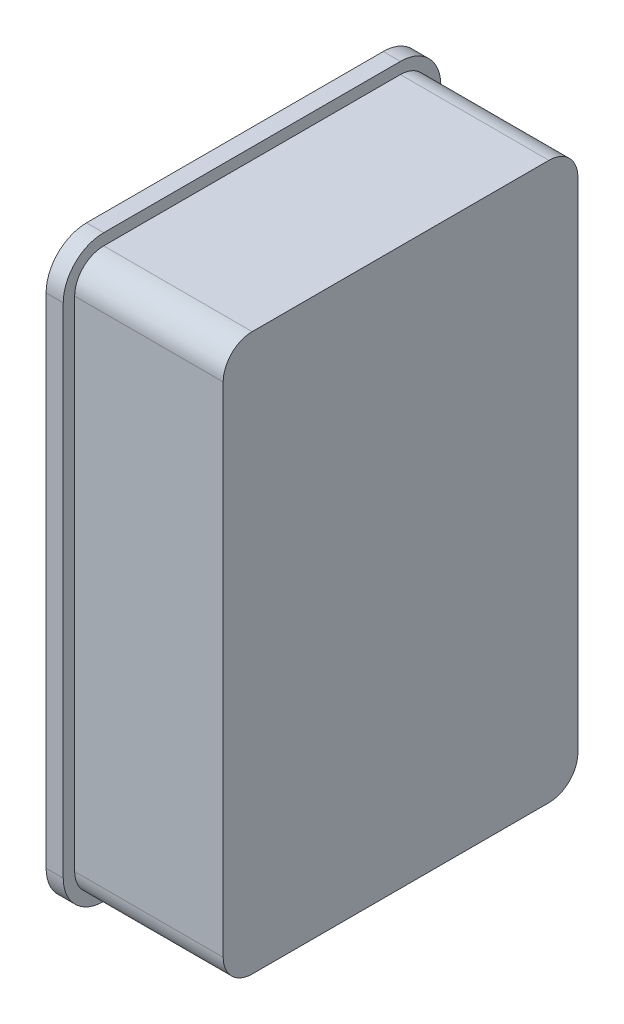
SolidWorks part; units mm, degrees
ref_plane "Top Plane" through (0, 0, 0) normal (0, 0, 1) x (1, 0, 0)
ref_plane "Right Plane" through (0, 0, 0) normal (0, 1, 0) x (1, 0, 0)
ref_plane "Front Plane" through (0, 0, 0) normal (1, 0, 0) x (0, 0, -1)
ref_axis "x-axis" through (-88.99, 0, 0) along (1, 0, 0)
ref_axis "y-axis" through (0, -55, 0) along (0, 1, 0)
ref_axis "z-axis" through (0, 0, 55) along (0, 0, -1)
sketch "Sketch2" plane through (0, 0, 0) normal (1, 0, 0) x (0, -1, 0)
  line L8 (6.35, 2.54) -> (6.35, 28.51)
  line L9 (3.81, 31.05) -> (-39.81, 31.05)
  line L10 (-42.35, 28.51) -> (-42.35, 2.54)
  line L11 (-39.81, 0) -> (3.81, 0)
  line L12 (0, 21.525) -> (0, 9.525)
  line L13 (0, 9.525) -> (-36, 9.525)
  line L14 (-36, 9.525) -> (-36, 21.525)
  line L15 (-36, 21.525) -> (0, 21.525)
  arc A8 (3.81, 0) -> (6.35, 2.54) centre (3.81, 2.54) ccw
  arc A9 (6.35, 28.51) -> (3.81, 31.05) centre (3.81, 28.51) ccw
  arc A10 (-39.81, 31.05) -> (-42.35, 28.51) centre (-39.81, 28.51) ccw
  arc A11 (-42.35, 2.54) -> (-39.81, 0) centre (-39.81, 2.54) ccw
  point P13 (0, 0)
  point P18 (-35.9164, 9.525)
extrude "Boss-Extrude2" add sketch "Sketch2" along normal blind 12
sketch "Sketch3" plane through (12, 0, 0) normal (1, 0, 0) x (0, 1, 0)
  line L4 (-6.35, -2.54) -> (-6.35, -28.51)
  line L5 (-3.81, -31.05) -> (39.81, -31.05)
  line L6 (42.35, -28.51) -> (42.35, -2.54)
  line L7 (39.81, 0) -> (-3.81, 0)
  line L8 (-6.35, -2.54) -> (-6.35, -28.51)
  line L9 (-3.81, -31.05) -> (39.81, -31.05)
  line L10 (42.35, -28.51) -> (42.35, -2.54)
  line L11 (39.81, 0) -> (-3.81, 0)
  arc A4 (-3.81, 0) -> (-6.35, -2.54) centre (-3.81, -2.54) ccw
  arc A5 (-6.35, -28.51) -> (-3.81, -31.05) centre (-3.81, -28.51) ccw
  arc A6 (39.81, -31.05) -> (42.35, -28.51) centre (39.81, -28.51) ccw
  arc A7 (42.35, -2.54) -> (39.81, 0) centre (39.81, -2.54) ccw
  arc A8 (-3.81, 0) -> (-6.35, -2.54) centre (-3.81, -2.54) ccw
  arc A9 (-6.35, -28.51) -> (-3.81, -31.05) centre (-3.81, -28.51) ccw
  arc A10 (39.81, -31.05) -> (42.35, -28.51) centre (39.81, -28.51) ccw
  arc A11 (42.35, -2.54) -> (39.81, 0) centre (39.81, -2.54) ccw
  dimension "D1" = 0
extrude "Boss-Extrude3" add sketch "Sketch3" along normal blind 1
sketch "Sketch6" plane through (0, 0, 0) normal (-1, 0, 0) x (0, -1, 0)
  line L0 (6.35, -2.54) -> (6.35, -28.51) construction
  line L1 (3.81, -31.05) -> (-39.81, -31.05) construction
  line L2 (-42.35, -28.51) -> (-42.35, -2.54) construction
  line L3 (-39.81, 0) -> (3.81, 0) construction
  line L4 (6.35, -2.54) -> (6.35, -28.51)
  line L5 (3.81, -31.05) -> (-39.81, -31.05)
  line L6 (-42.35, -28.51) -> (-42.35, -2.54)
  line L7 (-39.81, 0) -> (3.81, 0)
  line L8 (7.35, -2.54) -> (7.35, -28.51)
  line L9 (3.81, -32.05) -> (-39.81, -32.05)
  line L10 (-43.35, -28.51) -> (-43.35, -2.54)
  line L11 (-39.81, 1) -> (3.81, 1)
  arc A0 (6.35, -2.54) -> (3.81, 0) centre (3.81, -2.54) ccw construction
  arc A1 (3.81, -31.05) -> (6.35, -28.51) centre (3.81, -28.51) ccw construction
  arc A2 (-42.35, -28.51) -> (-39.81, -31.05) centre (-39.81, -28.51) ccw construction
  arc A3 (-39.81, 0) -> (-42.35, -2.54) centre (-39.81, -2.54) ccw construction
  arc A4 (6.35, -2.54) -> (3.81, 0) centre (3.81, -2.54) ccw
  arc A5 (3.81, -31.05) -> (6.35, -28.51) centre (3.81, -28.51) ccw
  arc A6 (-42.35, -28.51) -> (-39.81, -31.05) centre (-39.81, -28.51) ccw
  arc A7 (-39.81, 0) -> (-42.35, -2.54) centre (-39.81, -2.54) ccw
  arc A8 (3.81, -32.05) -> (7.35, -28.51) centre (3.81, -28.51) ccw
  arc A9 (-43.35, -28.51) -> (-39.81, -32.05) centre (-39.81, -28.51) ccw
  arc A10 (-39.81, 1) -> (-43.35, -2.54) centre (-39.81, -2.54) ccw
  arc A11 (7.35, -2.54) -> (3.81, 1) centre (3.81, -2.54) ccw
  dimension "D1" = 1
extrude "Boss-Extrude5" add sketch "Sketch6" along normal blind 1.5 separate body
ref_plane "Plane1" through (0, 18, 0) normal (0, 1, 0) x (1, 0, 0)
ref_plane "Plane2" through (0, 0, -15.525) normal (0, 0, -1) x (-1, 0, 0)
sketch "Sketch10" plane through (0, 18, 0) normal (0, 1, 0) x (1, 0, 0)
  line L0 (-1.1, 0) -> (-1.1, 2)
  line L1 (-1.1, 2) -> (-1.5, 1.6)
  line L2 (-1.5, 1.6) -> (-1.5, 0)
  line L3 (-1.5, 0) -> (-1.1, 0)
  line L4 (0, 0) -> (0, 2.54)
  line L5 (-1.5, 0) -> (0, 0)
  line L6 (-1.5, 2.54) -> (-1.5, 0)
  line L7 (0, 2.54) -> (-1.5, 2.54)
  line L8 (0, 0) -> (0, 2.54) construction
  line L9 (-1.5, 0) -> (0, 0) construction
  line L10 (-1.5, 2.54) -> (-1.5, 0) construction
  line L11 (0, 2.54) -> (-1.5, 2.54) construction
  line L12 (6.6, 15.525) -> (-6.6, 15.525) construction
  line L13 (0, 28.51) -> (-1.5, 28.51) construction
  line L14 (-1.5, 28.51) -> (-1.5, 31.05) construction
  line L15 (-1.5, 31.05) -> (0, 31.05) construction
  line L16 (0, 31.05) -> (0, 28.51) construction
  line L17 (-1.5, 31.05) -> (-1.1, 31.05)
  line L18 (-1.5, 30.45) -> (-1.5, 31.05)
  line L19 (-1.1, 30.05) -> (-1.5, 30.45)
  line L20 (-1.1, 31.05) -> (-1.1, 30.05)
  point P6 (0, 0)
  point P8 (0, 0)
  point P9 (-1.1, 1.9969)
  point P10 (0, 0)
  point P11 (-2, 0.5851)
  point P21 (0, 0)
  point P22 (0, 0)
  point P23 (0, 0)
  point P24 (-1.5, 29.95)
  point P25 (-1.5, 29.95)
  point P26 (-1.5, 31.05)
  point P27 (-1.5, 31.05)
  point P28 (-1.5, 29.55)
  point P29 (-1.5, 29.55)
  point P30 (-1.1, 29.95)
  point P31 (0, 0)
  point P32 (-1.048, 29.95)
  point P33 (-1.1125, 29.95)
  point P34 (-1.131, 29.2746)
  point P35 (-1.1, 29.2755)
  point P36 (0, 0)
  dimension "D2" = 1.1
  dimension "D3" = 2
  dimension "D4" = 45
  dimension "D5" = 45
  dimension "D6" = 1.1
  dimension "D7" = 1
  dimension "D1" = 0
extrude "Boss-Extrude10" add sketch "Sketch10" along normal up to surface and the other way up to surface up to face at (-0.75, 42.35, -15.525) other way up to face at (-0.75, -6.35, -15.525)
sketch "Sketch15" plane through (-1.5, 0, 0) normal (-1, 0, 0) x (0, -1, 0)
  line L4 (7.35, -28.51) -> (7.35, -2.54)
  line L5 (-39.81, -32.05) -> (3.81, -32.05)
  line L6 (-43.35, -2.54) -> (-43.35, -28.51)
  line L7 (3.81, 1) -> (-39.81, 1)
  arc A1 (7.35, -2.54) -> (6.35, -0.0742) centre (3.81, -2.54) ccw construction
  arc A2 (3.81, -32.05) -> (6.2758, -31.05) centre (3.81, -28.51) ccw construction
  arc A3 (-43.35, -28.51) -> (-42.35, -30.9758) centre (-39.81, -28.51) ccw construction
  arc A4 (6.35, -30.9758) -> (7.35, -28.51) centre (3.81, -28.51) ccw construction
  arc A5 (7.35, -2.54) -> (3.81, 1) centre (3.81, -2.54) ccw
  arc A6 (3.81, -32.05) -> (7.35, -28.51) centre (3.81, -28.51) ccw
  arc A7 (-43.35, -28.51) -> (-39.81, -32.05) centre (-39.81, -28.51) ccw
  arc A8 (-39.81, 1) -> (-43.35, -2.54) centre (-39.81, -2.54) ccw
  arc A9 (-42.2758, -31.05) -> (-39.81, -32.05) centre (-39.81, -28.51) ccw construction
  arc A10 (6.2758, 0) -> (3.81, 1) centre (3.81, -2.54) ccw construction
  point P0 (3.81, 1)
extrude "cut off extra edges" cut sketch "Sketch15" against normal blind 47 flip side to cut
